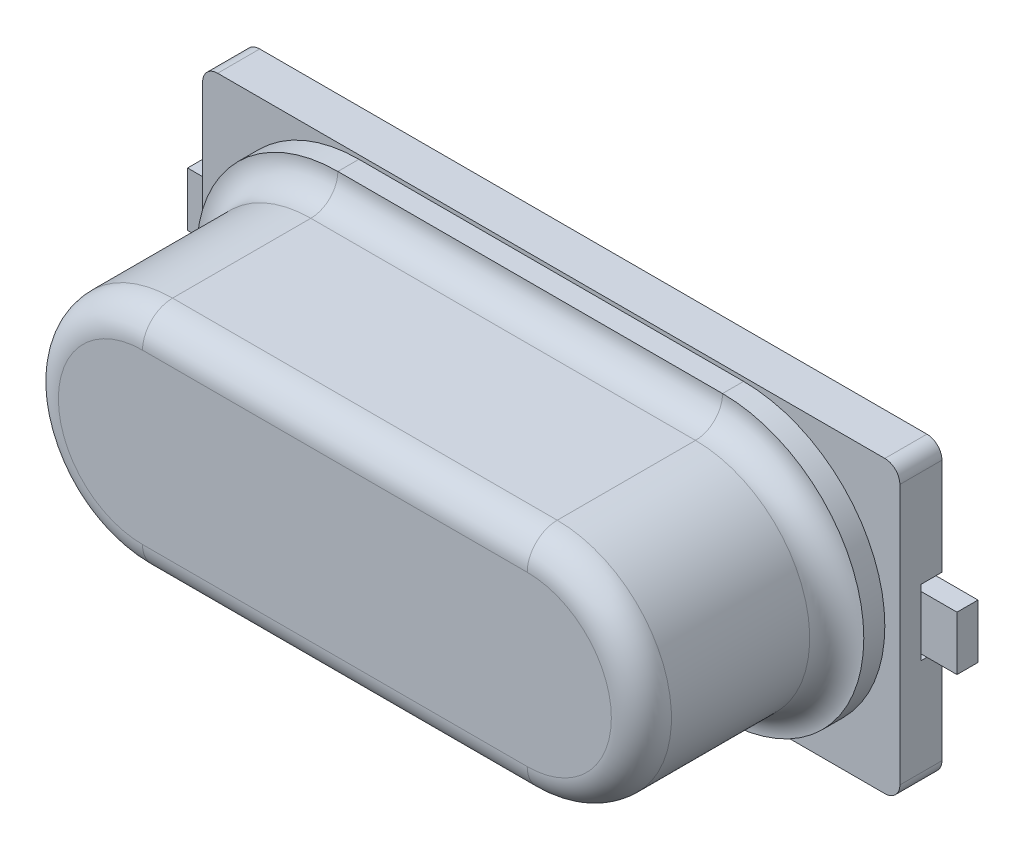
SolidWorks part; units mm, degrees
ref_plane "Top Plane" through (0, 0, 0) normal (0, 0, 1) x (1, 0, 0)
ref_plane "Front Plane" through (0, 0, 0) normal (0, 1, 0) x (1, 0, 0)
ref_plane "Right Plane" through (0, 0, 0) normal (1, 0, 0) x (0, 0, -1)
sketch "Sketch1" plane through (0, 0, 0) normal (0, 0, 1) x (1, 0, 0)
  line L0 (5.8, 0.55) -> (5.8, 2.415)
  line L1 (-5.8, -2.415) -> (5.8, -2.415)
  line L2 (-5.8, -2.415) -> (-5.8, -0.55)
  line L3 (-5.8, 2.415) -> (5.8, 2.415)
  line L4 (5.8, -2.415) -> (5.8, -0.55)
  line L5 (-5.8, -2.415) -> (5.8, 2.415) construction
  line L6 (-5.8, 2.415) -> (5.8, -2.415) construction
  line L7 (5.8, -0.55) -> (5.8, 0.55)
  line L8 (-5.8, 0.55) -> (-5.8, 2.415)
  line L9 (-5.8, -0.55) -> (-5.8, 0.55)
  line L10 (5.8, 0) -> (-5.8, 0) construction
  line L11 (5.8, 0.55) -> (2.35, 0.55)
  line L12 (2.35, 0.55) -> (2.35, -0.55)
  line L13 (2.35, -0.55) -> (5.8, -0.55)
  line L14 (-5.8, -0.55) -> (-2.35, -0.55)
  line L15 (-2.35, -0.55) -> (-2.35, 0.55)
  line L16 (-2.35, 0.55) -> (-5.8, 0.55)
  point P0 (0, 0)
  dimension "D1" = 11.6
  dimension "D2" = 4.83
  dimension "D3" = 1.1
  dimension "D4" = 4.7
extrude "Boss-Extrude3" add sketch "Sketch1" along normal blind 0.7 contours L12 L13 L7 L11 | L15 L16 L9 L14 | L16 L15 L14 L2 L1 L4 L13 L12 L11 L0 L3 L8 region at (0, 0, 0) region at (4.075, 0, 0) region at (-4.075, 0, 0)
extrude "Cut-Extrude1" cut sketch "Sketch1<3>" along normal blind 0.35 contours L12 L13 L7 L11 | L15 L16 L9 L14 region at (4.075, 0, 0) region at (-4.075, 0, 0)
sketch "Sketch1<3>" plane through (0, 0, 0) normal (0, 0, 1) x (1, 0, 0) same geometry as "Sketch1"
sketch "Sketch2" plane through (0, 0, 0) normal (0, 0, 1) x (1, 0, 0)
  line L0 (5.8, 0) -> (-5.8, 0) construction
  line L1 (2.45, -0.45) -> (6.4, -0.45)
  line L2 (2.45, -0.45) -> (2.45, 0.45)
  line L3 (2.45, 0.45) -> (6.4, 0.45)
  line L4 (6.4, -0.45) -> (6.4, 0.45)
  line L5 (2.45, -0.45) -> (6.4, 0.45) construction
  line L6 (2.45, 0.45) -> (6.4, -0.45) construction
  line L7 (2.35, 0.55) -> (2.35, -0.55) construction
  line L8 (-2.45, -0.45) -> (-6.4, -0.45)
  line L9 (-2.45, -0.45) -> (-2.45, 0.45)
  line L10 (-2.45, 0.45) -> (-6.4, 0.45)
  line L11 (-6.4, -0.45) -> (-6.4, 0.45)
  line L12 (-2.45, -0.45) -> (-6.4, 0.45) construction
  line L13 (-2.45, 0.45) -> (-6.4, -0.45) construction
  line L14 (5.8, 0.55) -> (2.35, 0.55) construction
  line L15 (0, 2.415) -> (0, -2.415) construction
  line L16 (-5.8, 2.415) -> (5.8, 2.415) construction
  line L17 (-5.8, -2.415) -> (5.8, -2.415) construction
  point P0 (4.425, 0)
  point P7 (-4.425, 0)
  dimension "D1" = 0.1
  dimension "D2" = 0.1
  dimension "D3" = 12.8
extrude "Boss-Extrude4" add sketch "Sketch2" along normal blind 0.35
sketch "Sketch3" plane through (0, 0, 0.7) normal (0, 0, 1) x (1, 0, 0)
  line L0 (-3.2, 0) -> (3.2, 0) construction
  line L1 (-3.2, 2.35) -> (3.2, 2.35)
  line L2 (-3.2, -2.35) -> (3.2, -2.35)
  arc A0 (-3.2, 2.35) -> (-3.2, -2.35) centre (-3.2, 0) ccw
  arc A1 (3.2, -2.35) -> (3.2, 2.35) centre (3.2, 0) ccw
  point P2 (0, 0)
  dimension "D1" = 4.7
  dimension "D2" = 11.1
extrude "Boss-Extrude5" add sketch "Sketch3" along normal blind 0.35
sketch "Sketch4" plane through (0, 0, 1.05) normal (0, 0, 1) x (1, 0, 0)
  line L0 (-3.2, 0) -> (3.2, 0) construction
  line L1 (-3.2, 1.9) -> (3.2, 1.9)
  line L2 (-3.2, -1.9) -> (3.2, -1.9)
  arc A0 (-3.2, 1.9) -> (-3.2, -1.9) centre (-3.2, 0) ccw
  arc A1 (3.2, -1.9) -> (3.2, 1.9) centre (3.2, 0) ccw
  arc A2 (3.2, -2.35) -> (3.2, 2.35) centre (3.2, 0) ccw construction
  point P2 (0, 0)
  dimension "D1" = 3.8
extrude "Boss-Extrude6" add sketch "Sketch4" along normal offset from surface (3.25 mm away) 4.3 up to plane "Top Plane"
fillet "Fillet1" radius 0.5 4 edges at (5.1, 0, 4.3) (0, -1.9, 4.3) (-5.1, 0, 4.3) (0, 1.9, 4.3)
fillet "Fillet2" radius 0.45 4 edges at (-5.1, 0, 1.05) (0, 1.9, 1.05) (5.1, 0, 1.05) (0, -1.9, 1.05)
fillet "Fillet3" radius 0.25 4 edges at (5.8, 2.415, 0.35) (5.8, -2.415, 0.35) (-5.8, 2.415, 0.35) (-5.8, -2.415, 0.35)
